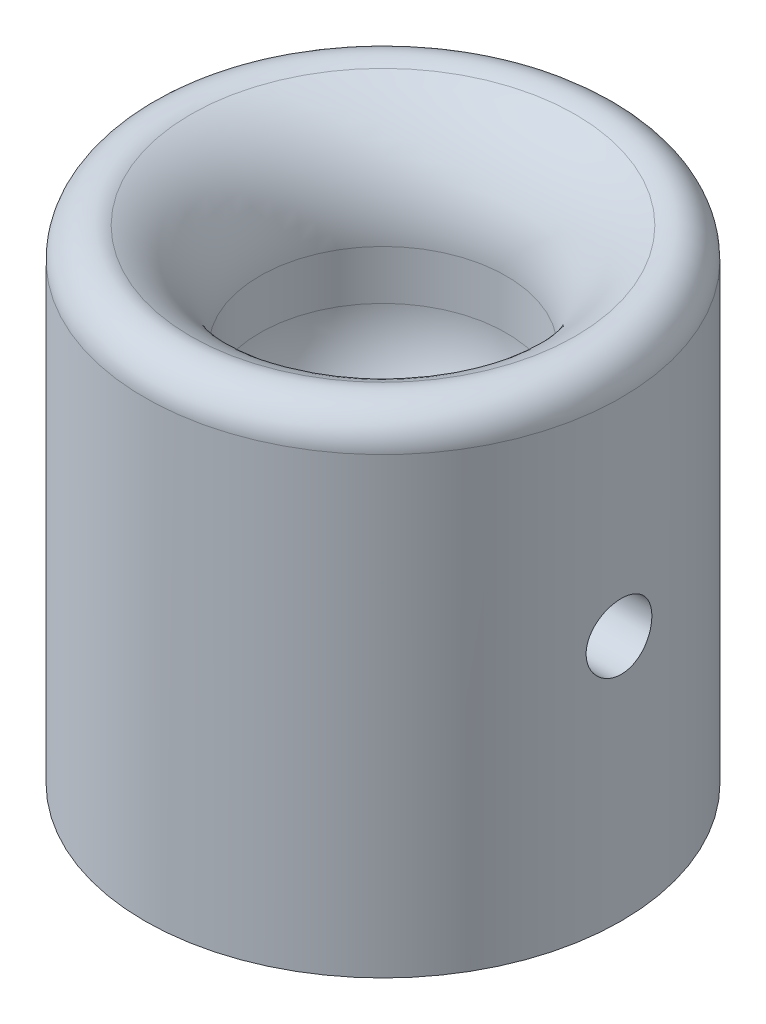
SolidWorks part; units mm, degrees
ref_plane "Plano frontal" through (0, 0, 0) normal (0, 0, 1) x (1, 0, 0)
ref_plane "Plano superior" through (0, 0, 0) normal (0, 1, 0) x (1, 0, 0)
ref_plane "Plano direito" through (0, 0, 0) normal (1, 0, 0) x (0, 0, -1)
sketch "Esboço1" plane through (0, 0, 0) normal (0, 1, 0) x (1, 0, 0)
  line L0 (0, 11.1182) -> (0, -10.5439) construction
  circle A0 centre (0, 0) radius 14.5
  circle A1 centre (-7.25, 0) radius 2
  circle A2 centre (0, 0) radius 3.175
  circle A3 centre (7.25, 0) radius 2
  dimension "D1" = 6.35
  dimension "D2" = 4
  dimension "D3" = 29
  dimension "D4" = 7.25
extrude "Ressalto-extrusão1" add sketch "Esboço1" along normal blind 30 contours A0
sketch "Esboço3" plane through (0, 30, 0) normal (0, 1, 0) x (1, 0, 0)
  circle A0 centre (0, 0) radius 7.5
  dimension "D1" = 15
extrude "Corte-extrusão3" cut sketch "Esboço3" against normal blind 17
fillet "Filete1" radius 7 2 edges at (0, 30, 7.5) (0, 13, 7.5)
fillet "Filete2" radius 2 1 edges at (0, 30, 14.5)
sketch "Esboço2" plane through (0, 0, 0) normal (1, 0, 0) x (0, 0, -1)
  circle A0 centre (0, 15) radius 2
  point P2 (0, 0)
  dimension "D1" = 4
  dimension "D2" = 15
extrude "Corte-extrusão1" cut sketch "Esboço2" against normal through all both and the other way through all
extrude "Corte-extrusão2" cut sketch "Esboço1<3>" along normal blind 10 contours A1 | A2 L0 | L0 A2 | A3 region at (1.3475, 0, 0) region at (-1.3475, 0, 0) region at (-7.25, 0, 0) region at (7.25, 0, 0)
sketch "Esboço1<3>" plane through (0, 0, 0) normal (0, 1, 0) x (1, 0, 0) same geometry as "Esboço1"
